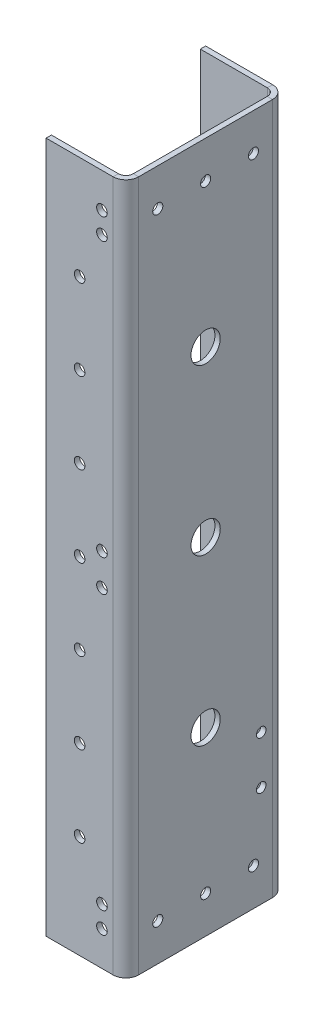
SolidWorks part; units mm, degrees
note: The reader was unsure of these and kept them because the rebuilt part matched: flange length of "Edge-Flange1".
material "Plain Carbon Steel"
ref_plane "Front Plane" through (0, 0, 0) normal (0, 0, 1) x (1, 0, 0)
ref_plane "Top Plane" through (0, 0, 0) normal (0, 1, 0) x (1, 0, 0)
ref_plane "Right Plane" through (0, 0, 0) normal (1, 0, 0) x (0, 0, -1)
sketch "Sketch1" plane through (0, 0, 0) normal (1, 0, 0) x (0, 0, -1)
  line L1 (-150, -650) -> (150, -650)
  line L2 (-150, -650) -> (-150, 650)
  line L3 (-150, 650) -> (150, 650)
  line L4 (150, -650) -> (150, 650)
  line L5 (-150, -650) -> (150, 650) construction
  line L6 (-150, 650) -> (150, -650) construction
  point P0 (0, 0)
  dimension "D1" = 300
  dimension "D2" = 1300
base flange "Base-Flange1" sketch "Sketch1" thickness 10 reverse thickness direction no parameters "D1"=3
edge flange "Edge-Flange1" sketch "Sketch10" flange profiles "Sketch10", "Sketch11" flange angle 90 flange length 150 flange position material inside bend radius 14 thickness 10 relief rectangular parameters "D6"=10, "D8"=1
sketch "Sketch10" plane through (-10, 0, 150) normal (0, 0, 1) x (0, 1, 0)
  line L0 (650, 0) -> (-650, 0) construction
  line L1 (650, 0) -> (-650, 0)
  line L2 (-650, 0) -> (-650, 140)
  line L3 (-650, 140) -> (650, 140)
  line L4 (650, 140) -> (650, 0)
sketch "Sketch11" plane through (-10, 0, -150) normal (0, 0, -1) x (0, -1, 0)
  line L0 (650, 0) -> (-650, 0) construction
  line L1 (650, 0) -> (-650, 0)
  line L2 (-650, 0) -> (-650, 140)
  line L3 (-650, 140) -> (650, 140)
  line L4 (650, 140) -> (650, 0)
bend "EdgeBend1" bend radius 14 bend angle 90 parameters "D5"=1
bend "EdgeBend2" bend radius 14 bend angle 90 parameters "D5"=2
sketch "Sketch12" plane through (0, 0, 0) normal (1, 0, 0) x (0, 0, -1)
  line L0 (-150, 650) -> (150, 650) construction
  line L1 (150, -650) -> (150, 650) construction
  circle A0 centre (90, 580) radius 9.5
  circle A1 centre (0, 580) radius 9.5
  dimension "D2" = 60
  dimension "D3" = 19
  dimension "D1" = 70
extrude "Cut-Extrude1" cut sketch "Sketch12" against normal blind 10
mirror "Mirror1" about plane through (0, 0, 0) normal (0, 1, 0) of "Cut-Extrude1"
mirror "Mirror2" about plane through (0, 0, 0) normal (0, 0, 1) of "Mirror1", "Cut-Extrude1"
sketch "Sketch13" plane through (0, 0, 0) normal (1, 0, 0) x (0, 0, -1)
  line L0 (-150, 650) -> (150, 650) construction
  circle A0 centre (0, 310) radius 27.5
  dimension "D1" = 55
  dimension "D2" = 340
extrude "Cut-Extrude2" cut sketch "Sketch13" against normal blind 10
pattern_linear "LPattern1" count 3 spacing 310 along (0, -1, 0) of "Cut-Extrude2"
sketch "Sketch14" plane through (0, 0, -150) normal (0, 0, -1) x (-1, 0, 0)
  line L0 (10, -650) -> (150, -650) construction
  line L1 (24, -650) -> (150, -650) construction
  circle A0 centre (87, -456) radius 10
  point P8 (87, -650)
  dimension "D1" = 20
  dimension "D2" = 194
extrude "Cut-Extrude3" cut sketch "Sketch14" against normal through all
pattern_linear "LPattern2" count 7 spacing 152 along (0, 1, 0) of "Cut-Extrude3"
sketch "Sketch18" plane through (0, 0, -150) normal (0, 0, -1) x (-1, 0, 0)
  circle A0 centre (45, 545) radius 10
  circle A1 centre (45, 585) radius 10
  circle A2 centre (45, 30) radius 10
  dimension "D2" = 20
  dimension "D4" = 40
  dimension "D1" = 45
  dimension "D3" = 30
  dimension "D5" = 585
extrude "Cut-Extrude4" cut sketch "Sketch18" against normal through all
mirror "Mirror3" about plane through (0, 0, 0) normal (0, 1, 0) of "Cut-Extrude4"
sketch "Sketch19" plane through (0, 0, 0) normal (1, 0, 0) x (0, 0, -1)
  line L2 (126, 650) -> (-126, 650) construction
  circle A0 centre (-105, 445) radius 9
  dimension "D1" = 18
  dimension "D3" = 205
sketch "Sketch20" plane through (0, 0, 0) normal (1, 0, 0) x (0, 0, -1)
  circle A0 centre (104.55, -370) radius 9 construction
  circle A1 centre (104.55, -370) radius 9
  circle A2 centre (104.55, -460) radius 9 construction
  circle A3 centre (104.55, -460) radius 9
extrude "Cut-Extrude5" cut sketch "Sketch20" against normal blind 10
sketch "Bend-Lines1" [suppressed] plane through (0, 0, 0) normal (0, 1, 0) x (1, 0, 0)
sketch "Bounding-Box1" [suppressed] plane through (0, 0, 0) normal (0, 1, 0) x (1, 0, 0)
sheet metal parameters "Sheet-Metal1" thickness 10 parameters "D1"=3
flat pattern "Flat-Pattern1" [suppressed]
sketch "Bend-Lines2" plane through (0, 0, 0) normal (0, 1, 0) x (1, 0, 0)
sketch3d "Bounding-Box2" [suppressed]
  line L0 (150, 800, 0) -> (150, -800, 0) construction
  line L1 (-150, 800, 0) -> (-150, -800, 0) construction
  line L2 (150, 800, 0) -> (-150, 800, 0) construction
  line L3 (150, -800, 0) -> (-150, -800, 0) construction
sheet metal parameters "Sheet-Metal2" thickness 10 parameters "D1"=3
flat pattern "Flat-Pattern1"
sketch "Bend-Lines2" plane through (0, 0, 0) normal (1, 0, 0) x (0, 0, -1)
  line L0 (141.781, -800) -> (141.781, 800) construction
  line L1 (-141.781, 800) -> (-141.781, -800) construction
  line L2 (141.781, -800) -> (141.781, 800) construction
  line L3 (-141.781, 800) -> (-141.781, -800) construction
sketch3d "Bounding-Box2" [suppressed]
  line L0 (-283.5619, 800, 0) -> (-283.5619, -800, 0) construction
  line L1 (283.5619, 800, 0) -> (283.5619, -800, 0) construction
  line L2 (-283.5619, 800, 0) -> (283.5619, 800, 0) construction
  line L3 (-283.5619, -800, 0) -> (283.5619, -800, 0) construction
bend of the flat pattern "Flatten-<EdgeBend1>1"
bend of the flat pattern "Flatten-<EdgeBend2>1"
sheet metal parameters "Sheet-Metal3" thickness 10 parameters "D1"=3
flat pattern "Flat-Pattern1"
sketch "Bend-Lines2" plane through (0, 0, 0) normal (1, 0, 0) x (0, 0, -1)
  line L0 (141.781, -800) -> (141.781, 800) construction
  line L1 (-141.781, 800) -> (-141.781, -800) construction
  line L2 (141.781, -800) -> (141.781, 800) construction
  line L3 (-141.781, 800) -> (-141.781, -800) construction
sketch3d "Bounding-Box2" [suppressed]
  line L0 (-283.5619, 800, 0) -> (-283.5619, -800, 0) construction
  line L1 (283.5619, 800, 0) -> (283.5619, -800, 0) construction
  line L2 (-283.5619, 800, 0) -> (283.5619, 800, 0) construction
  line L3 (-283.5619, -800, 0) -> (283.5619, -800, 0) construction
bend of the flat pattern "Flatten-<EdgeBend1>1"
bend of the flat pattern "Flatten-<EdgeBend2>1"
sheet metal parameters "Sheet-Metal4" thickness 10 parameters "D1"=3
flat pattern "Flat-Pattern1"
sketch "Bend-Lines2" plane through (0, 0, 0) normal (1, 0, 0) x (0, 0, -1)
  line L0 (141.781, -800) -> (141.781, 800) construction
  line L1 (-141.781, 800) -> (-141.781, -800) construction
  line L2 (141.781, -800) -> (141.781, 800) construction
  line L3 (-141.781, 800) -> (-141.781, -800) construction
sketch3d "Bounding-Box2" [suppressed]
  line L0 (-283.5619, 800, 0) -> (-283.5619, -800, 0) construction
  line L1 (283.5619, 800, 0) -> (283.5619, -800, 0) construction
  line L2 (-283.5619, 800, 0) -> (283.5619, 800, 0) construction
  line L3 (-283.5619, -800, 0) -> (283.5619, -800, 0) construction
bend of the flat pattern "Flatten-<EdgeBend1>1"
bend of the flat pattern "Flatten-<EdgeBend2>1"
sheet metal parameters "Sheet-Metal5" thickness 10 parameters "D1"=3
flat pattern "Flat-Pattern1"
sketch "Bend-Lines2" plane through (0, 0, 0) normal (1, 0, 0) x (0, 0, -1)
  line L0 (141.781, -800) -> (141.781, 800) construction
  line L1 (-141.781, 800) -> (-141.781, -800) construction
  line L2 (141.781, -800) -> (141.781, 800) construction
  line L3 (-141.781, 800) -> (-141.781, -800) construction
sketch3d "Bounding-Box2" [suppressed]
  line L0 (-283.5619, 800, 0) -> (-283.5619, -800, 0) construction
  line L1 (283.5619, 800, 0) -> (283.5619, -800, 0) construction
  line L2 (-283.5619, 800, 0) -> (283.5619, 800, 0) construction
  line L3 (-283.5619, -800, 0) -> (283.5619, -800, 0) construction
bend of the flat pattern "Flatten-<EdgeBend1>1"
bend of the flat pattern "Flatten-<EdgeBend2>1"
sheet metal parameters "Sheet-Metal6" thickness 10 parameters "D1"=3
flat pattern "Flat-Pattern1"
sketch "Bend-Lines2" plane through (0, 0, 0) normal (1, 0, 0) x (0, 0, -1)
  line L0 (141.781, -800) -> (141.781, 800) construction
  line L1 (-141.781, 800) -> (-141.781, -800) construction
  line L2 (141.781, -800) -> (141.781, 800) construction
  line L3 (-141.781, 800) -> (-141.781, -800) construction
sketch3d "Bounding-Box2" [suppressed]
  line L0 (-283.5619, 800, 0) -> (-283.5619, -800, 0) construction
  line L1 (283.5619, 800, 0) -> (283.5619, -800, 0) construction
  line L2 (-283.5619, 800, 0) -> (283.5619, 800, 0) construction
  line L3 (-283.5619, -800, 0) -> (283.5619, -800, 0) construction
bend of the flat pattern "Flatten-<EdgeBend1>1"
bend of the flat pattern "Flatten-<EdgeBend2>1"
sheet metal parameters "Sheet-Metal7" thickness 10 parameters "D1"=3
flat pattern "Flat-Pattern1"
sketch "Bend-Lines2" plane through (0, 0, 0) normal (1, 0, 0) x (0, 0, -1)
  line L0 (141.781, -800) -> (141.781, 800) construction
  line L1 (-141.781, 800) -> (-141.781, -800) construction
  line L2 (141.781, -800) -> (141.781, 800) construction
  line L3 (-141.781, 800) -> (-141.781, -800) construction
sketch3d "Bounding-Box2" [suppressed]
  line L0 (-283.5619, 800, 0) -> (-283.5619, -800, 0) construction
  line L1 (283.5619, 800, 0) -> (283.5619, -800, 0) construction
  line L2 (-283.5619, 800, 0) -> (283.5619, 800, 0) construction
  line L3 (-283.5619, -800, 0) -> (283.5619, -800, 0) construction
bend of the flat pattern "Flatten-<EdgeBend1>1"
bend of the flat pattern "Flatten-<EdgeBend2>1"
sheet metal parameters "Sheet-Metal8" thickness 10 parameters "D1"=3
flat pattern "Flat-Pattern1"
sketch "Bend-Lines2" plane through (0, 0, 0) normal (1, 0, 0) x (0, 0, -1)
  line L0 (141.781, -800) -> (141.781, 800) construction
  line L1 (-141.781, 800) -> (-141.781, -800) construction
  line L2 (141.781, -800) -> (141.781, 800) construction
  line L3 (-141.781, 800) -> (-141.781, -800) construction
sketch3d "Bounding-Box2" [suppressed]
  line L0 (-283.5619, 800, 0) -> (-283.5619, -800, 0) construction
  line L1 (283.5619, 800, 0) -> (283.5619, -800, 0) construction
  line L2 (-283.5619, 800, 0) -> (283.5619, 800, 0) construction
  line L3 (-283.5619, -800, 0) -> (283.5619, -800, 0) construction
bend of the flat pattern "Flatten-<EdgeBend1>1"
bend of the flat pattern "Flatten-<EdgeBend2>1"
sheet metal parameters "Sheet-Metal9" thickness 10 parameters "D1"=3
flat pattern "Flat-Pattern1" [suppressed]
sketch "Bend-Lines2" plane through (0, 0, 0) normal (1, 0, 0) x (0, 0, -1)
  line L0 (140.9226, -800) -> (140.9226, 800) construction
  line L1 (-140.9226, 800) -> (-140.9226, -800) construction
  line L2 (140.9226, -800) -> (140.9226, 800) construction
  line L3 (-140.9226, 800) -> (-140.9226, -800) construction
sketch3d "Bounding-Box2" [suppressed]
  line L0 (-281.8451, 800, 0) -> (-281.8451, -800, 0) construction
  line L1 (281.8451, 800, 0) -> (281.8451, -800, 0) construction
  line L2 (-281.8451, 800, 0) -> (281.8451, 800, 0) construction
  line L3 (-281.8451, -800, 0) -> (281.8451, -800, 0) construction
bend of the flat pattern "Flatten-<EdgeBend1>1"
bend of the flat pattern "Flatten-<EdgeBend2>1"
sketch "Sketch16-1" [suppressed] plane through (0, 0, 131.8451) normal (1, 0, 0) x (0, 0, -1)
  line L0 (-150, 800) -> (-10, 800) construction
  line L1 (-18.1549, -800) -> (-18.1549, 800) construction
  line L5 (-50, 760) -> (-50, 700) construction
  line L6 (-50, 700) -> (-110, 700) construction
  circle A1 centre (-50, 700) radius 10 construction
  circle A2 centre (-50, 760) radius 10
  circle A3 centre (-110, 700) radius 10
  circle A4 centre (-110, 760) radius 10
  dimension "D1" = 40
  dimension "D2" = 20
  dimension "D5" = 60
  dimension "D3" = 60
  dimension "D4" = 91.8451
sheet metal parameters "Sheet-Metal13" thickness 10 parameters "D1"=3
flat pattern "Flat-Pattern1"
sketch "Bend-Lines2" plane through (0, 0, 0) normal (1, 0, 0) x (0, 0, -1)
  line L0 (140.9226, -800) -> (140.9226, 800) construction
  line L1 (-140.9226, 800) -> (-140.9226, -800) construction
  line L2 (140.9226, -800) -> (140.9226, 800) construction
  line L3 (-140.9226, 800) -> (-140.9226, -800) construction
sketch3d "Bounding-Box2" [suppressed]
  line L0 (-281.8451, 800, 0) -> (-281.8451, -800, 0) construction
  line L1 (281.8451, 800, 0) -> (281.8451, -800, 0) construction
  line L2 (-281.8451, 800, 0) -> (281.8451, 800, 0) construction
  line L3 (-281.8451, -800, 0) -> (281.8451, -800, 0) construction
bend of the flat pattern "Flatten-<EdgeBend1>1"
bend of the flat pattern "Flatten-<EdgeBend2>1"
sheet metal parameters "Sheet-Metal14" thickness 10 parameters "D1"=3
flat pattern "Flat-Pattern1"
sketch "Bend-Lines2" plane through (0, 0, 0) normal (1, 0, 0) x (0, 0, -1)
  line L0 (140.9226, -650) -> (140.9226, 650) construction
  line L1 (-140.9226, 650) -> (-140.9226, -650) construction
  line L2 (140.9226, -650) -> (140.9226, 650) construction
  line L3 (-140.9226, 650) -> (-140.9226, -650) construction
sketch3d "Bounding-Box2" [suppressed]
  line L0 (-281.8451, 650, 0) -> (-281.8451, -650, 0) construction
  line L1 (281.8451, 650, 0) -> (281.8451, -650, 0) construction
  line L2 (-281.8451, 650, 0) -> (281.8451, 650, 0) construction
  line L3 (-281.8451, -650, 0) -> (281.8451, -650, 0) construction
bend of the flat pattern "Flatten-<EdgeBend1>1"
bend of the flat pattern "Flatten-<EdgeBend2>1"
sheet metal parameters "Sheet-Metal19" thickness 10 parameters "D1"=3
flat pattern "Flat-Pattern1"
sketch "Bend-Lines2" plane through (0, 0, 0) normal (1, 0, 0) x (0, 0, -1)
  line L0 (140.9226, -650) -> (140.9226, 650) construction
  line L1 (-140.9226, 650) -> (-140.9226, -650) construction
  line L2 (140.9226, -650) -> (140.9226, 650) construction
  line L3 (-140.9226, 650) -> (-140.9226, -650) construction
sketch3d "Bounding-Box2" [suppressed]
  line L0 (-281.8451, 650, 0) -> (-281.8451, -650, 0) construction
  line L1 (281.8451, 650, 0) -> (281.8451, -650, 0) construction
  line L2 (-281.8451, 650, 0) -> (281.8451, 650, 0) construction
  line L3 (-281.8451, -650, 0) -> (281.8451, -650, 0) construction
bend of the flat pattern "Flatten-<EdgeBend1>1"
bend of the flat pattern "Flatten-<EdgeBend2>1"
